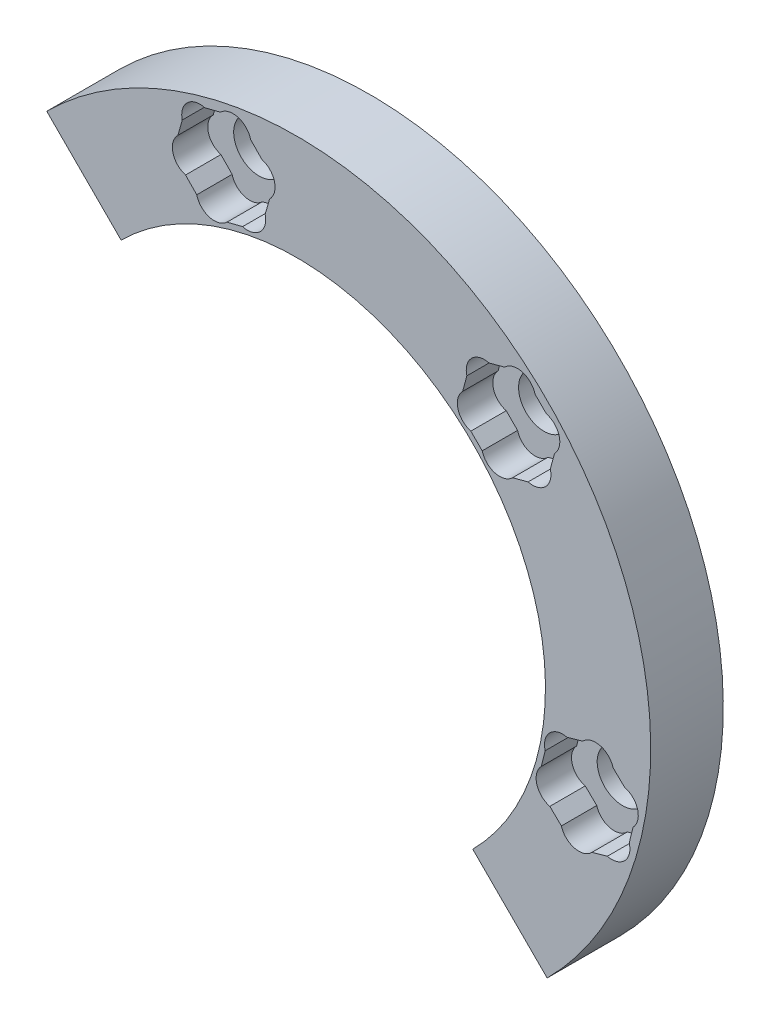
SolidWorks part; units mm, degrees
ref_plane "Front Plane" through (0, 0, 0) normal (0, 0, 1) x (1, 0, 0)
ref_plane "Top Plane" through (0, 0, 0) normal (0, 1, 0) x (1, 0, 0)
ref_plane "Right Plane" through (0, 0, 0) normal (1, 0, 0) x (0, 0, -1)
sketch "Sketch1" plane through (0, 0, 0) normal (0, 0, 1) x (1, 0, 0)
  line L0 (78.7927, 51.2155) -> (74.6902, 55.3155)
  line L2 (51.2155, 78.7927) -> (55.3155, 74.6902)
  arc A0 (78.7927, 51.2155) -> (51.2155, 78.7927) centre (65, 65) ccw construction
  arc A1 (78.7927, 51.2155) -> (51.2155, 78.7927) centre (65, 65) ccw
  circle A2 centre (60.9677, 80.9997) radius 1.4 construction
  circle A3 centre (76.6673, 76.6673) radius 1.4 construction
  circle A4 centre (80.9997, 60.9677) radius 1.4 construction
  circle A5 centre (60.9677, 80.9997) radius 1.4
  circle A6 centre (76.6673, 76.6673) radius 1.4
  circle A7 centre (80.9997, 60.9677) radius 1.4
  circle A8 centre (65, 65) radius 13.7
  circle A9 centre (65, 65) radius 13.5 construction
  dimension "D1" = 0.2
extrude "Shape" add sketch "Sketch1" along normal blind 4 contours A8 L0 A1 L2 A7 A6 A5 region at (77.0742, 53.5985, 0)
sketch "Sketch2" plane through (0, 0, 4) normal (0, 0, 1) x (1, 0, 0)
  line L0 (53.2655, 76.7415) -> (60.9677, 80.9997) construction
  line L1 (63.7669, 81.7052) -> (61.7563, 83.7766)
  line L2 (61.7563, 83.7766) -> (58.9571, 83.0712)
  line L3 (58.9571, 83.0712) -> (58.1684, 80.2942)
  line L4 (58.1684, 80.2942) -> (60.179, 78.2228)
  line L5 (60.179, 78.2228) -> (62.9782, 78.9282)
  line L6 (62.9782, 78.9282) -> (63.7669, 81.7052)
  line L7 (51.2155, 78.7927) -> (55.3155, 74.6902) construction
  line L8 (65, 65) -> (60.9677, 80.9997) construction
  line L9 (65, 65) -> (80.9997, 60.9677) construction
  line L10 (78.9282, 62.9782) -> (78.2228, 60.179)
  line L11 (78.2228, 60.179) -> (80.2942, 58.1684)
  line L12 (60.9677, 80.9997) -> (76.6673, 76.6673) construction
  line L13 (80.2942, 58.1684) -> (83.0712, 58.9571)
  line L14 (83.0712, 58.9571) -> (83.7766, 61.7563)
  line L15 (58.1684, 80.2942) -> (63.7669, 81.7052) construction
  line L16 (65, 65) -> (76.6673, 76.6673) construction
  line L17 (78.7085, 74.626) -> (79.4556, 77.4144)
  line L18 (79.4556, 77.4144) -> (77.4144, 79.4556)
  line L19 (77.4144, 79.4556) -> (74.626, 78.7085)
  line L20 (74.626, 78.7085) -> (73.8789, 75.9201)
  line L21 (73.8789, 75.9201) -> (75.9201, 73.8789)
  line L22 (75.9201, 73.8789) -> (78.7085, 74.626)
  line L23 (83.7766, 61.7563) -> (81.7052, 63.7669)
  line L24 (81.7052, 63.7669) -> (78.9282, 62.9782)
  line L25 (78.7085, 74.626) -> (74.626, 78.7085) construction
  line L26 (80.2942, 58.1684) -> (81.7052, 63.7669) construction
  circle A0 centre (60.9677, 80.9997) radius 2.5 construction
  circle A1 centre (79.1847, 60.4522) radius 1
  circle A2 centre (59.1381, 80.5386) radius 1
  circle A3 centre (59.6536, 82.3536) radius 1
  circle A4 centre (61.4831, 82.8147) radius 1
  circle A5 centre (62.7972, 81.4608) radius 1
  circle A6 centre (62.2818, 79.6458) radius 1
  circle A7 centre (60.4522, 79.1847) radius 1
  circle A8 centre (76.6673, 76.6673) radius 2.5 construction
  circle A9 centre (65, 65) radius 13.7
  arc A10 (74.6902, 55.3155) -> (55.3155, 74.6902) centre (65, 65) ccw construction
  circle A11 centre (80.9997, 60.9677) radius 2.5 construction
  circle A12 centre (78.0014, 75.3331) radius 1
  circle A13 centre (80.5386, 59.1381) radius 1
  circle A14 centre (76.1789, 74.8448) radius 1
  circle A15 centre (74.8448, 76.1789) radius 1
  circle A16 centre (75.3331, 78.0014) radius 1
  circle A17 centre (77.1556, 78.4897) radius 1
  circle A18 centre (78.4897, 77.1556) radius 1
  circle A19 centre (79.6458, 62.2818) radius 1
  circle A20 centre (81.4608, 62.7972) radius 1
  circle A21 centre (82.8147, 61.4831) radius 1
  circle A22 centre (82.3536, 59.6536) radius 1
  point P26 (0, 0)
  point P39 (60.9677, 80.9997)
  point P66 (76.6673, 76.6673)
  point P76 (80.9997, 60.9677)
  dimension "D2" = 2
  dimension "D1" = 5
  dimension "D3" = 6
  dimension "D4" = 6
  dimension "D5" = 6
extrude "Nut cuts" cut sketch "Sketch2" against normal blind 1.95 contours A3 | A4 | A5 | A6 | A7 | A2 | L5 L6 L1 L2 L3 L4 | L20 L21 L22 L17 L18 L19 | A17 | A16 | A15 | A14 | A12 | A18 | L13 L14 L23 L24 L10 L11 | A13 | A1 | A19 | A20 | A21 | A22
